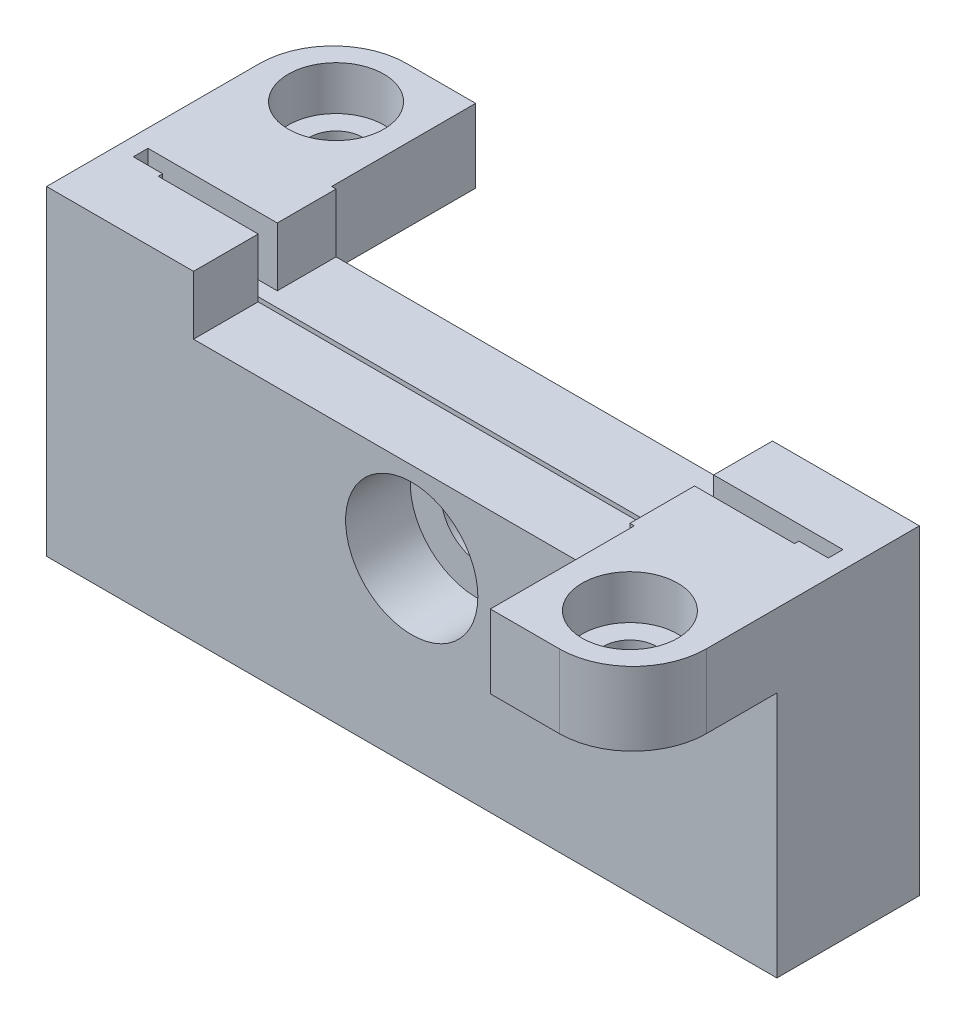
SolidWorks part; units mm, degrees
ref_plane "Front Plane" through (0, 0, 0) normal (0, 0, 1) x (1, 0, 0)
ref_plane "Top Plane" through (0, 0, 0) normal (0, 1, 0) x (1, 0, 0)
ref_plane "Right Plane" through (0, 0, 0) normal (1, 0, 0) x (0, 0, -1)
sketch "Sketch1" plane through (0, 0, 0) normal (0, 0, 1) x (1, 0, 0)
  line L0 (0, 0) -> (0, 21.8)
  line L1 (0, 21.8) -> (10, 21.8)
  line L2 (10, 21.8) -> (10, 17.8)
  line L3 (10, 17.8) -> (39.7, 17.8)
  line L4 (39.7, 17.8) -> (39.7, 21.8)
  line L5 (39.7, 21.8) -> (49.7, 21.8)
  line L6 (49.7, 21.8) -> (49.7, 0)
  line L7 (49.7, 0) -> (0, 0)
  dimension "D1" = 21.8
  dimension "D2" = 49.7
  dimension "D3" = 4
  dimension "D4" = 10
extrude "Boss-Extrude1" add sketch "Sketch1" along normal mid plane 9.7
sketch "Sketch2" plane through (0, 21.8, 0) normal (0, 1, 0) x (1, 0, 0)
  line L0 (24.85, 4.85) -> (24.85, -4.85) construction
  line L1 (39.7, 4.85) -> (10, 4.85) construction
  line L2 (39.7, -4.85) -> (10, -4.85) construction
  line L4 (3.2, -0.45) -> (46.5, -0.45)
  line L5 (3.2, -0.45) -> (3.2, -0.15)
  line L6 (3.2, -0.15) -> (46.5, -0.15)
  line L7 (46.5, -0.45) -> (46.5, -0.15)
  line L8 (3.2, -0.45) -> (46.5, -0.15) construction
  line L9 (3.2, -0.15) -> (46.5, -0.45) construction
  point P6 (24.85, -0.3)
  point P13 (24.85, 0)
  dimension "D1" = 0.3
  dimension "D2" = 43.3
  dimension "D3" = 0.3
extrude "Cut-Extrude1" cut sketch "Sketch2" against normal blind 21
sketch "Sketch3" plane through (0, 21.8, 0) normal (0, 1, 0) x (1, 0, 0)
  line L6 (0, 4.85) -> (9.7, 4.85)
  line L8 (0, 4.85) -> (0, 9.65)
  line L9 (5, 14.65) -> (9.7, 14.65)
  line L11 (9.7, 4.85) -> (9.7, 14.65)
  line L12 (49.7, -4.85) -> (49.7, 4.85) construction
  line L13 (40, -4.85) -> (49.7, -4.85)
  line L14 (40, -4.85) -> (40, -14.65)
  line L15 (40, -14.65) -> (44.7, -14.65)
  line L16 (49.7, -4.85) -> (49.7, -9.65)
  line L17 (49.7, -4.85) -> (39.7, -4.85) construction
  arc A0 (44.7, -14.65) -> (49.7, -9.65) centre (44.7, -9.65) ccw
  arc A1 (0, 9.65) -> (5, 14.65) centre (5, 9.65) cw
  point P17 (0, 14.65)
  line M28 (10, 4.85) -> (0, 4.85)
  dimension "D2" = 5
  dimension "D1" = 9.8
  dimension "D3" = 9.7
extrude "Boss-Extrude2" add sketch "Sketch3" against normal blind 5 contours L11 | L11 L9 L8 M28 | L16 L13 L14 L15 region at (5.0733, 21.8, -9.5237) region at (44.6267, 21.8, 9.5237)
sketch "Sketch5" plane through (0, 21.8, 0) normal (0, 1, 0) x (1, 0, 0)
  point P0 (44.85, -10)
  point P1 (4.85, 10)
hole_wizard "CBORE for M3 SHCS1" positions "Sketch5" profile "Sketch6" counterbore size "M3" standard "ANSI Metric" end condition up to next
sketch "Sketch6" plane through (44.85, 21.8, 10) normal (1, 0, 0) x (0, 0, 1)
  line L0 (0, 0) -> (0, 5)
  line L1 (0, 5) -> (1.8, 5)
  line L3 (1.8, 5) -> (1.8, 3)
  line L4 (1.8, 3) -> (3.25, 3)
  line L5 (3.25, 3) -> (3.25, 0)
  line L7 (3.25, 0) -> (0, 0)
  line L11 (0, -6.35) -> (0, 107.95) construction
  dimension "Thru Hole Dia." = 3.6
  dimension "Thru Hole Depth" = 5
  dimension "C'Bore Dia." = 6.5
  dimension "C'Bore Depth" = 3
sketch "Sketch7" plane through (0, 0, -4.85) normal (0, 0, -1) x (-1, 0, 0)
  line L0 (0, 0) -> (-49.7, 0) construction
  line L1 (-29.642, 12.3) -> (-27.246, 8.15)
  line L2 (-27.246, 8.15) -> (-22.454, 8.15)
  line L3 (-22.454, 8.15) -> (-20.058, 12.3)
  line L4 (-20.058, 12.3) -> (-22.454, 16.45)
  line L5 (-22.454, 16.45) -> (-27.246, 16.45)
  line L6 (-27.246, 16.45) -> (-29.642, 12.3)
  line L7 (-46.5, 0.8) -> (-3.2, 0.8) construction
  circle A0 centre (-24.85, 12.3) radius 4.15 construction
  point P11 (-24.85, 0)
  dimension "D1" = 8.3
  dimension "D2" = 11.5
extrude "Cut-Extrude2" cut sketch "Sketch7" against normal blind 4
sketch "Sketch9" plane through (0, 0, 4.85) normal (0, 0, 1) x (1, 0, 0)
  circle A0 centre (24.85, 12.3) radius 4.5
  dimension "D1" = 9
extrude "Cut-Extrude3" cut sketch "Sketch9" against normal up to next
sketch "Sketch10" plane through (0, 21.8, 0) normal (0, 1, 0) x (1, 0, 0)
  line L0 (3.2, -0.15) -> (3.2, -0.45) construction
  line L1 (10, -0.15) -> (1.2, -0.15)
  line L2 (10, -0.15) -> (10, 0.85)
  line L3 (10, 0.85) -> (1.2, 0.85)
  line L4 (1.2, -0.15) -> (1.2, 0.85)
  line L5 (39.7, -0.15) -> (48.5, -0.15)
  line L6 (39.7, -0.15) -> (39.7, 0.85)
  line L7 (39.7, 0.85) -> (48.5, 0.85)
  line L8 (48.5, -0.15) -> (48.5, 0.85)
  line L9 (46.5, -0.15) -> (3.2, -0.15) construction
  line L10 (39.7, -0.15) -> (39.7, 4.85) construction
  point P14 (48.6505, -1.1)
  point P15 (39.9385, 0.7869)
  dimension "D1" = 2
  dimension "D2" = 1
extrude "Cut-Extrude4" cut sketch "Sketch10" against normal up to surface (4 mm away) up to face at (24.85, 17.8, 2.65)
sketch "Sketch11" plane through (0, 0, 0.15) normal (0, 0, 1) x (1, 0, 0)
  circle A0 centre (24.85, 12.3) radius 2.7
  dimension "D1" = 5.4
extrude "Cut-Extrude5" cut sketch "Sketch11" against normal up to surface (1 mm away) up to face at (24.85, 12.3, -0.85)
